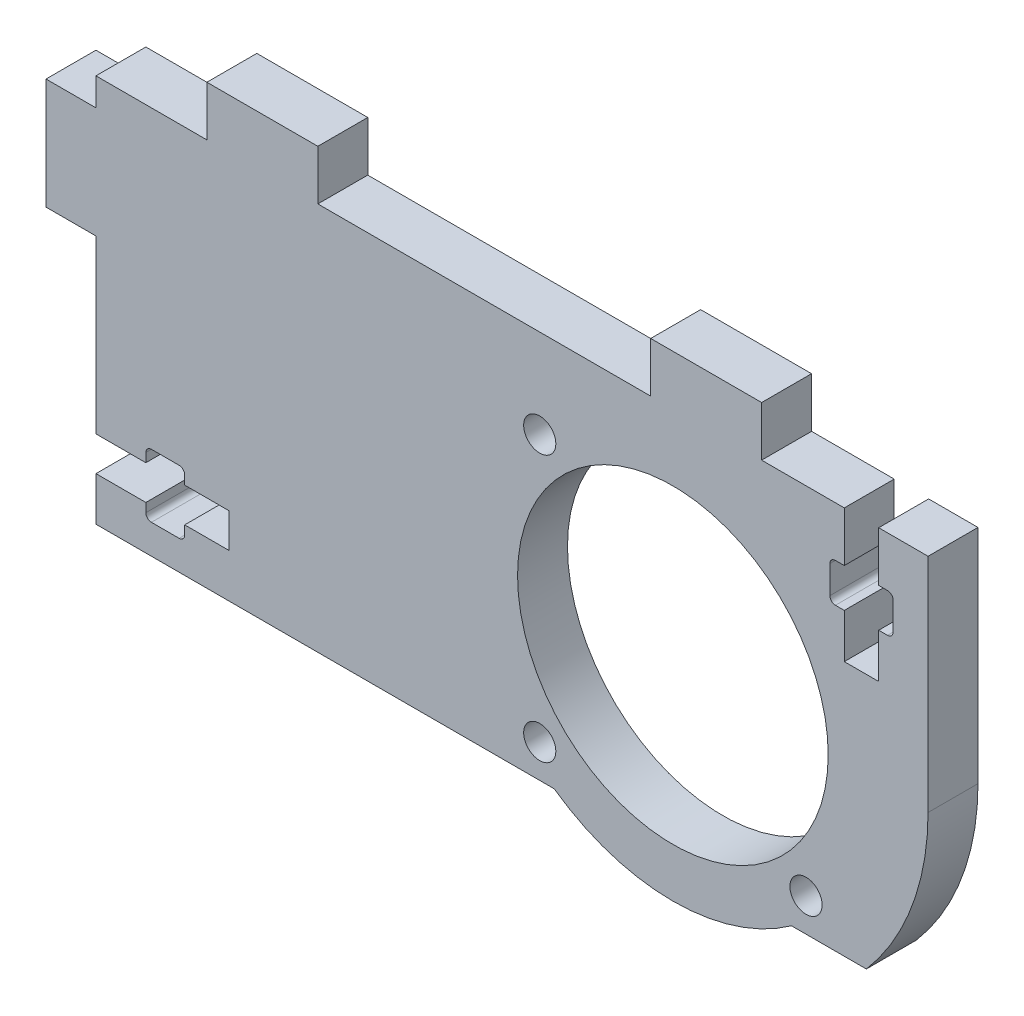
SolidWorks part; units mm, degrees
ref_plane "Front Plane" through (0, 0, 0) normal (0, 0, 1) x (1, 0, 0)
ref_plane "Top Plane" through (0, 0, 0) normal (0, 1, 0) x (1, 0, 0)
ref_plane "Right Plane" through (0, 0, 0) normal (1, 0, 0) x (0, 0, -1)
sketch "Sketch1" plane through (0, 0, 0) normal (0, 0, 1) x (1, 0, 0)
  line L0 (0, 0) -> (0, -35)
  line L1 (0, -35) -> (75, -35)
  line L2 (75, -35) -> (75, 0)
  line L3 (75, 0) -> (0, 0)
  dimension "D1" = 75
  dimension "D2" = 35
extrude "MainShape" add sketch "Sketch1" along normal blind 4.5
sketch "Sketch2" plane through (0, 0, 4.5) normal (0, 0, 1) x (1, 0, 0)
  line L0 (0, -2.5) -> (-4.5, -2.5)
  line L1 (0, 0) -> (0, -35) construction
  line L2 (-4.5, -2.5) -> (-4.5, -12.5)
  line L3 (-4.5, -12.5) -> (0, -12.5)
  line L4 (0, -12.5) -> (0, -2.5)
  line L5 (-4.5, -7.5) -> (0, -7.5) construction
  dimension "D1" = 10
  dimension "D2" = 4.5
  dimension "D3" = 7.5
extrude "RearTab" add sketch "Sketch2" against normal through all
sketch "Sketch3" plane through (0, 0, 4.5) normal (0, 0, 1) x (1, 0, 0)
  line L0 (75, 0) -> (0, 0) construction
  line L1 (10, 0) -> (20, 0)
  line L2 (10, 0) -> (10, 4.5)
  line L3 (10, 4.5) -> (20, 4.5)
  line L4 (20, 0) -> (20, 4.5)
  line L5 (15, 4.5) -> (15, 0) construction
  line L6 (50, 0) -> (60, 0)
  line L7 (50, 0) -> (50, 4.5)
  line L8 (50, 4.5) -> (60, 4.5)
  line L9 (60, 0) -> (60, 4.5)
  line L10 (55, 4.5) -> (55, 0) construction
  dimension "D1" = 4.5
  dimension "D2" = 10
  dimension "D3" = 40
  dimension "D4" = 15
extrude "Boss-Extrude3" add sketch "Sketch3" against normal through all
sketch "Sketch4" plane through (0, 0, 4.5) normal (0, 0, 1) x (1, 0, 0)
  line L0 (69, 0) -> (69, -12) construction
  line L1 (75, 0) -> (60, 0) construction
  line L2 (70.55, -12) -> (67.45, -12) construction
  line L3 (67.45, -12) -> (67.45, 0) construction
  line L4 (67.45, 0) -> (67.45, -4.5)
  line L5 (67.45, -4.5) -> (66.65, -4.5)
  line L6 (66.15, -5) -> (66.15, -7.5)
  line L7 (66.65, -8) -> (67.45, -8)
  line L8 (67.45, -8) -> (67.45, -12)
  line L9 (67.45, -12) -> (70.55, -12)
  line L10 (67.45, 0) -> (70.55, 0)
  line L11 (70.55, -12) -> (70.55, 0) construction
  line L12 (70.55, -8) -> (70.55, -12)
  line L13 (71.35, -8) -> (70.55, -8)
  line L14 (71.85, -5) -> (71.85, -7.5)
  line L15 (70.55, -4.5) -> (71.35, -4.5)
  line L16 (70.55, 0) -> (70.55, -4.5)
  arc A0 (66.15, -7.5) -> (66.65, -8) centre (66.65, -7.5) ccw
  arc A1 (66.65, -4.5) -> (66.15, -5) centre (66.65, -5) ccw
  arc A2 (71.35, -4.5) -> (71.85, -5) centre (71.35, -5) cw
  arc A3 (71.85, -7.5) -> (71.35, -8) centre (71.35, -7.5) cw
  point P13 (66.15, -8)
  point P16 (66.15, -4.5)
  point P27 (71.85, -4.5)
  point P28 (71.85, -8)
  dimension "D7" = 0.5
  dimension "D1" = 12
  dimension "D2" = 1.55
  dimension "D3" = 3.5
  dimension "D4" = 2.85
  dimension "D5" = 8
  dimension "D6" = 69
extrude "Cut-Extrude1" cut sketch "Sketch4" against normal through all
sketch "Sketch5" plane through (0, 0, 4.5) normal (0, 0, 1) x (1, 0, 0)
  line L0 (45.0208, 0) -> (45.0208, 4.5) construction
  line L1 (42.5416, 0) -> (47.5, 0)
  line L2 (42.5416, 0) -> (42.5416, -5.18)
  line L3 (42.5416, -5.18) -> (47.5, -5.18)
  line L4 (47.5, 0) -> (47.5, -5.18)
  line L5 (42.5416, 0) -> (47.5, -5.18) construction
  line L6 (42.5416, -5.18) -> (47.5, 0) construction
  line L7 (42, -4.18) -> (48, -4.18) construction
  line L8 (50, 0) -> (20, 0) construction
  line L9 (48, -4.18) -> (48, -1.18) construction
  line L10 (48, -2.68) -> (58, -2.68) construction
  line L11 (48, -4.18) -> (48, -1.18) construction
  line L12 (58, -1.18) -> (58, -4.18) construction
  line L13 (53, -2.68) -> (53, 0) construction
  line L14 (0, 0) -> (19.5, 0) construction
  line L15 (63.4584, -5.18) -> (58.5, 0) construction
  line L16 (63.4584, 0) -> (58.5, -5.18) construction
  line L17 (58.5, 0) -> (58.5, -5.18)
  line L18 (63.4584, -5.18) -> (58.5, -5.18)
  line L19 (63.4584, 0) -> (63.4584, -5.18)
  line L20 (63.4584, 0) -> (58.5, 0)
  line L21 (42.5416, -5.18) -> (47.5, 0) construction
  point P0 (45.0208, -2.59)
  point P27 (60.9792, -2.59)
  dimension "D1" = 1
  dimension "D2" = 0
  dimension "D3" = 0.5
extrude "Cut-Extrude2" [suppressed] cut sketch "Sketch5" against normal through all
sketch "Sketch6" plane through (0, 0, 4.5) normal (0, 0, 1) x (1, 0, 0)
  line L0 (52, -20) -> (40, -8) construction
  line L2 (52, -34) -> (52, -6) construction
  line L3 (52, -20) -> (38, -20) construction
  line L4 (52, -20) -> (64, -8) construction
  line L5 (52, -20) -> (64, -32) construction
  line L6 (52, -20) -> (40, -32) construction
  circle A0 centre (52, -20) radius 14
  circle A1 centre (40, -8) radius 1.45
  circle A3 centre (64, -32) radius 1.45
  circle A4 centre (40, -32) radius 1.45
  dimension "D1" = 28
  dimension "D4" = 2.9
  dimension "D2" = 52
  dimension "D3" = 20
  dimension "D5" = 12
  dimension "D6" = 45
extrude "Cut-Extrude3" cut sketch "Sketch6" against normal through all
sketch "Sketch7" plane through (0, 0, 4.5) normal (0, 0, 1) x (1, 0, 0)
  line L0 (0, -35) -> (62.6919, -35)
  arc A0 (41.3081, -35) -> (62.6919, -35) centre (52, -20) ccw
  circle A1 centre (52, -20) radius 14 construction
  circle A2 centre (64, -32) radius 1.45 construction
extrude "Boss-Extrude4" add sketch "Sketch7" against normal through all contours L0 A0 region at (52, -36.3797, 4.5)
sketch "Sketch8" [suppressed] plane through (0, 0, 4.5) normal (0, 0, 1) x (1, 0, 0)
  line L1 (0, -35) -> (39.1367, -35) construction
  line L18 (15, -35) -> (15, -9.316) construction
  line L19 (6.3379, -28.8128) -> (15, -37.4749) construction
  line L20 (8.8128, -26.3379) -> (17.4749, -35) construction
  line L21 (6.3379, -28.8128) -> (8.8128, -26.3379) construction
  line L22 (15, -35) -> (7.5754, -27.5754) construction
  line L23 (15, -37.4749) -> (11.0756, -33.5504)
  line L24 (11.0756, -33.5504) -> (10.1917, -34.4343)
  line L25 (10.1917, -34.4343) -> (7.2218, -31.4645)
  line L26 (7.2218, -31.4645) -> (8.1057, -30.5806)
  line L27 (8.1057, -30.5806) -> (6.3379, -28.8128)
  line L28 (15, -37.4749) -> (15, -35)
  line L29 (17.4749, -35) -> (15, -35)
  line L30 (8.8128, -26.3379) -> (6.3379, -28.8128)
  line L31 (10.5806, -28.1057) -> (8.8128, -26.3379)
  line L32 (11.4645, -27.2218) -> (10.5806, -28.1057)
  line L33 (14.4343, -30.1917) -> (11.4645, -27.2218)
  line L34 (13.5504, -31.0756) -> (14.4343, -30.1917)
  line L35 (17.4749, -35) -> (13.5504, -31.0756)
  dimension "D7" = 15
extrude "Cut-Extrude4" [suppressed] cut sketch "Sketch8" against normal through all
sketch "Sketch10" [suppressed] plane through (0, 0, 4.5) normal (0, 0, 1) x (1, 0, 0)
  line L0 (17.4749, -35) -> (21.7175, -30.7574)
  line L1 (21.7175, -30.7574) -> (25.253, -34.2929)
  line L2 (25.253, -34.2929) -> (24.5459, -35)
  line L3 (17.4749, -35) -> (39.1367, -35) construction
  line L4 (24.5459, -35) -> (17.4749, -35)
  line L5 (17.4749, -35) -> (13.5504, -31.0756) construction
  dimension "D1" = 5
  dimension "D2" = 6
extrude "Cut-Extrude6" [suppressed] cut sketch "Sketch10" against normal through all
sketch "Sketch12" plane through (0, 0, 4.5) normal (0, 0, 1) x (1, 0, 0)
  line L0 (7.3224, -34.6526) -> (32.3224, -34.6526) construction
  circle A0 centre (32.3224, -34.6526) radius 5
  circle A1 centre (7.3224, -34.6526) radius 5
  dimension "D1" = 10
  dimension "D2" = 10
  dimension "D3" = 25
  dimension "D4" = 34.6526
  dimension "D5" = 7.3224
extrude "Boss-Extrude5" [suppressed] add sketch "Sketch12" against normal through all
sketch "Sketch11" plane through (0, 0, 4.5) normal (0, 0, 1) x (1, 0, 0)
  line L0 (0, -29.5) -> (12, -29.5) construction
  line L1 (0, -12.5) -> (0, -35) construction
  line L2 (12, -31.05) -> (12, -27.95) construction
  line L3 (12, -27.95) -> (0, -27.95) construction
  line L4 (0, -31.05) -> (0, -27.95)
  line L5 (0, -27.95) -> (4.5, -27.95)
  line L6 (4.5, -27.95) -> (4.5, -27.15)
  line L7 (5, -26.65) -> (7.5, -26.65)
  line L8 (8, -27.15) -> (8, -27.95)
  line L9 (8, -27.95) -> (12, -27.95)
  line L10 (12, -27.95) -> (12, -31.05)
  line L11 (12, -31.05) -> (0, -31.05) construction
  line L12 (8, -31.05) -> (12, -31.05)
  line L13 (8, -31.85) -> (8, -31.05)
  line L14 (5, -32.35) -> (7.5, -32.35)
  line L15 (4.5, -31.05) -> (4.5, -31.85)
  line L16 (0, -31.05) -> (4.5, -31.05)
  line L17 (-4.5, -2.5) -> (-4.5, -12.5) construction
  arc A0 (7.5, -26.65) -> (8, -27.15) centre (7.5, -27.15) cw
  arc A1 (4.5, -27.15) -> (5, -26.65) centre (5, -27.15) cw
  arc A2 (4.5, -31.85) -> (5, -32.35) centre (5, -31.85) ccw
  arc A3 (7.5, -32.35) -> (8, -31.85) centre (7.5, -31.85) ccw
  point P12 (8, -26.65)
  point P15 (4.5, -26.65)
  point P26 (4.5, -32.35)
  point P27 (8, -32.35)
  point P28 (-4.5, -7.5)
  dimension "D1" = 12
  dimension "D2" = 1.55
  dimension "D3" = 3.5
  dimension "D4" = 2.85
  dimension "D5" = 8
  dimension "D6" = 0.5
  dimension "D7" = 22
extrude "Cut-Extrude7" cut sketch "Sketch11" against normal through all
sketch "Sketch13" [suppressed] plane through (0, 0, 4.5) normal (0, 0, 1) x (1, 0, 0)
  circle A0 centre (7.3224, -34.6526) radius 1.55
  circle A1 centre (32.3224, -34.6526) radius 1.55
  arc A2 (2.3345, -35) -> (12.3103, -35) centre (7.3224, -34.6526) ccw construction
  arc A3 (27.3345, -35) -> (37.3103, -35) centre (32.3224, -34.6526) ccw construction
  dimension "D1" = 2.9
extrude "Cut-Extrude8" [suppressed] cut sketch "Sketch13" against normal through all
sketch "Sketch14" plane through (0, 0, 4.5) normal (0, 0, 1) x (1, 0, 0)
  line L0 (75, -35) -> (75, 0) construction
  line L1 (69.4356, -35) -> (75, -35)
  line L2 (75, -35) -> (75, -20)
  arc A0 (69.4356, -35) -> (75, -20) centre (52, -20) ccw
  circle A1 centre (52, -20) radius 14 construction
extrude "SmoothEdge" cut sketch "Sketch14" against normal through all
equation "\"X-ROD-SPACING\"=45"
equation "\"Y-ROD-SPACING\"=75"
equation "\"Z-ROD-SPACING\"=17.5"
equation "\"Y-BED-OFFSET\"=2"
equation "\"Y-BED-ROD-INSET\"=3.5"
equation "\"Y-BED-SCREW-SPACING\"=209"
equation "\"Y-BED-SCREW-CUTOUT-SLOT-HEIGHT\"=2"
equation "\"T-SLOT-NUT-FILLET-RADIUS\"=0.5"
equation "\"T-SLOT-SCREW-SHAFT-RADIUS\"=1.55"
equation "\"T-SLOT-SCREW-SHAFT-CUTOUT-LENGTH\"=11.0"
equation "\"T-SLOT-NUT-DEPTH\"=3.5"
equation "\"T-SLOT-NUT-WIDTH\"=2.85"
equation "\"T-SLOT-NUT-END-DISTANCE\"=8"
equation "\"ACRYLIC-THICKNESS\"=10"
equation "\"ACRYLIC-THICKNESS2\"=4.5"
equation "\"ACRYLIC-TAB-CUTOUT-SIZE\"=\"ACRYLIC-THICKNESS\"+\"ACRYLIC-TAB-TOLERANCE\"*2"
equation "\"ACRYLIC-TAB-TOLERANCE\"=-.05"
equation "\"ACRYLIC-TAB-WIDTH\"=\"ACRYLIC-THICKNESS\""
equation "\"ACRYLIC-M3-HOLE\"=2.9"
equation "\"SMOOTHROD-CAP-SCREW-DISTANCE\"=20"
equation "\"FRAME-WIDTH-INNER\"=370"
equation "\"NEMA17-HOLE-SPACING\"=31"
equation "\"NEMA17-CENTRAL-CUTOUT\"=22.5"
equation "\"Z-BRACKET-REACH\"=55"
equation "\"Z-ROD-INSET\"=16"
equation "\"TOP-BRACKET-SPACING\"=40"
equation "\"SMOOTHROD-X-LENGTH\"=350"
equation "\"SMOOTHROD-Y-LENGTH\"=350"
equation "\"SMOOTHROD-Z-LENGTH\"=350"
equation "\"SMOOTHROD-TIGHTENING-HEADROOM\"=.25"
equation "\"LEADSCREW-Z-LENGTH\"=300"
equation "\"SCREW-LENGTH-FRAME\"=\"ACRYLIC-THICKNESS\" + 10"
equation "\"SCREW-LENGTH-MOTOR\"=\"ACRYLIC-THICKNESS\" + 5"
equation "\"SCREW-LENGTH-EXTRUDER\"=28"
equation "\"SCREW-HEAD-RADIUS\"=6"
equation "\"PRINTED-M3-HOLE\"=3.5"
equation "\"PRINTED-X-SMOOTHROD-DIAMETER\"=8.4"
equation "\"PRINTED-X-SMOOTHROD-CUTOUT\"=10"
equation "\"PRINTED-X-BASE-HEIGHT\"=10"
equation "\"PRINTED-LM8UU-CUTOUT-SIZE\"=15.5"
equation "\"PRINTED-LM8UU-CUTOUT-LENGTH\"=24.5"
equation "\"PRINTED-X-IDLER-HEIGHT\"=16"
equation "\"PRINTED-M3-NUT-AF\"=6.25"
equation "\"PSU-MOUNTING-WIDTH\"=95"
equation "\"PSU-MOUNTING-HEIGHT\"=177"
equation "\"Y-BELT-TO-ROD-DISTANCE\"=20"
equation "\"SPOOL-HOLDER-ROD-SPACING\"=150"
equation "\"ACRYLIC-X-CARRIAGE-WIDTH\"=55"
equation "\"ACRYLIC-X-CARRIAGE-HEIGHT\"=75"
equation "\"ACRYLIC-X-CARRIAGE-LM8UU-CUTOUT-WIDTH\"=24.25"
equation "\"ACRYLIC-X-CARRIAGE-LM8UU-CUTOUT-HEIGHT\"=11.0"
equation "\"ACRYLIC-X-CARRIAGE-SCREW-SPACING-X\"=15"
equation "\"ACRYLIC-X-CARRIAGE-SCREW-SPACING-Y\"=33"
equation "\"ACRYLIC-X-CARRIAGE-CENTER-TAB-SPACING\"=14"
equation "\"ACRYLIC-X-CARRIAGE-EXTRUDER-OFFSET\"=26"
equation "\"ACRYLIC-X-CARRIAGE-EXTRUDER-ANGLE\"=90"
equation "\"ACRYLIC-X-CARRIAGE-EXTRUDER-SHELF-DEPTH\"=\"ACRYLIC-X-CARRIAGE-EXTRUDER-OFFSET\" + 28"
equation "\"ACRYLIC-X-CARRIAGE-EXTRUDER-BRACE-SPACING\"=23"
equation "\"ACRYLIC-X-CARRIAGE-EXTRUDER-BRACE-TAB-OFFSET\"=20"
equation "\"ACRYLIC-X-CARRIAGE-EXTRUDER-BRACE-HEIGHT\"=35"
equation "\"ACRYLIC-X-CARRIAGE-EXTRUDER-BRACE-SCREW-SPACING\"=22"
equation "\"ACRYLIC-X-CARRIAGE-DUAL-WIDTH-MULTIPLIER\"=1.65"
equation "\"ACRYLIC-X-CARRIAGE-DUAL-HOTEND-SPACING\"=42"
equation "\"ACRYLIC-X-CARRIAGE-DUAL-WIDTH\"=75"
equation "\"ACRYLIC-X-CARRIAGE-DUAL-FAN-OFFSET\"=52"
equation "\"ACRYLIC-X-CARRIAGE-DUAL-FAN-HEIGHT\"=20"
equation "\"ACRYLIC-X-CARRIAGE-DUAL-HOTEND-SEPARATION\"=36"
equation "\"ACRYLIC-X-CARRIAGE-DUAL-MOUNT-PLATE-DEPTH\"=75"
equation "\"ACRYLIC-X-CARRIAGE-DUAL-MOUNT-BRACE-WIDTH\"=33"
equation "\"ACRYLIC-X-CARRIAGE-DUAL-MOUNT-SCREW-WIDTH\"=40"
equation "\"BLOWER-FAN-WIDTH\"=15"
equation "\"D1@Sketch1\"=\"ACRYLIC-X-CARRIAGE-DUAL-MOUNT-PLATE-DEPTH\""
equation "\"D2@Sketch1\"=\"ACRYLIC-X-CARRIAGE-EXTRUDER-BRACE-HEIGHT\""
equation "\"D1@MainShape\" = \"ACRYLIC-THICKNESS2\""
equation "\"D1@Sketch2\"=\"ACRYLIC-TAB-WIDTH\""
equation "\"D2@Sketch2\"=\"ACRYLIC-THICKNESS2\""
equation "\"D1@Sketch3\"=\"ACRYLIC-THICKNESS2\""
equation "\"D2@Sketch3\"=\"ACRYLIC-TAB-WIDTH\""
equation "\"D1@Sketch4\"=\"T-SLOT-SCREW-SHAFT-CUTOUT-LENGTH\"+1"
equation "\"D2@Sketch4\"=\"T-SLOT-SCREW-SHAFT-RADIUS\""
equation "\"D3@Sketch4\"=\"T-SLOT-NUT-DEPTH\""
equation "\"D4@Sketch4\"=\"T-SLOT-NUT-WIDTH\""
equation "\"D5@Sketch4\"=\"T-SLOT-NUT-END-DISTANCE\""
equation "\"D7@Sketch4\"=\"T-SLOT-NUT-FILLET-RADIUS\""
equation "\"D2@Sketch6\"=\"ACRYLIC-X-CARRIAGE-DUAL-FAN-OFFSET\""
equation "\"D3@Sketch6\"=\"ACRYLIC-X-CARRIAGE-DUAL-FAN-HEIGHT\""
equation "\"D4@Sketch6\"=\"ACRYLIC-M3-HOLE\""
equation "\"D1@Sketch11\"=\"T-SLOT-SCREW-SHAFT-CUTOUT-LENGTH\"+1"
equation "\"D2@Sketch11\"=\"T-SLOT-SCREW-SHAFT-RADIUS\""
equation "\"D3@Sketch11\"=\"T-SLOT-NUT-DEPTH\""
equation "\"D4@Sketch11\"=\"T-SLOT-NUT-WIDTH\""
equation "\"D5@Sketch11\"=\"T-SLOT-NUT-END-DISTANCE\""
equation "\"D6@Sketch11\"=\"T-SLOT-NUT-FILLET-RADIUS\""
equation "\"D1@Sketch13\"=\"ACRYLIC-M3-HOLE\""
